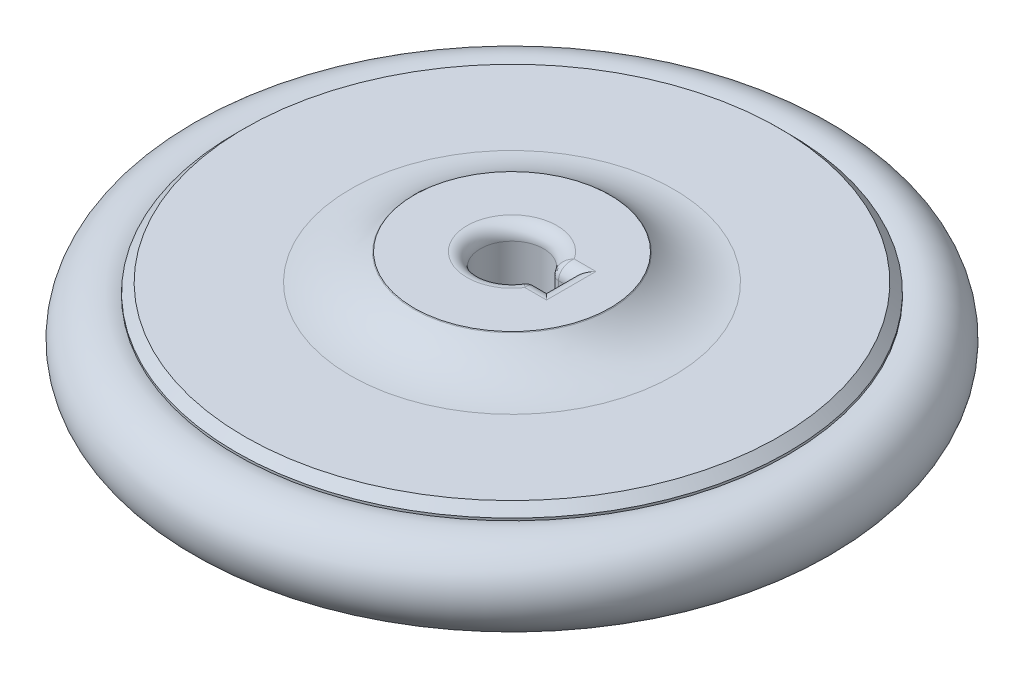
SolidWorks part; units mm, degrees
ref_plane "Спереди" through (0, 0, 0) normal (0, 0, 1) x (1, 0, 0)
ref_plane "Сверху" through (0, 0, 0) normal (0, 1, 0) x (1, 0, 0)
ref_plane "Справа" through (0, 0, 0) normal (1, 0, 0) x (0, 0, -1)
sketch "Эскиз1" plane through (0, 0, 0) normal (0, 1, 0) x (1, 0, 0)
  circle A0 centre (0, 0) radius 62
  dimension "D1" = 124
extrude "Бобышка-Вытянуть1" add sketch "Эскиз1" along normal blind 22
sketch "Эскиз3" plane through (0, 0, 0) normal (0, 0, 1) x (1, 0, 0)
  line L0 (0, 0) -> (0, 22) construction
  line L1 (62, 22) -> (-62, 22) construction
  line L2 (0, 22) -> (0, 11) construction
  line L3 (0, 11) -> (-84.2443, 11) construction
  line L9 (-56, -6.4426) -> (-56, 31.0537) construction
  circle A2 centre (-65, 11) radius 9
  dimension "D1" = 56
  dimension "D2" = 18
revolve "Вырез-Повернуть2" cut sketch "Эскиз3" angle 360 about L0
chamfer "Фаска3" distance 2 angle 45 1 edges at (0, 0, 62)
chamfer "Фаска2" distance 2 angle 45 1 edges at (0, 22, 62)
sketch "Эскиз4" plane through (0, 22, 0) normal (0, 1, 0) x (1, 0, 0)
  circle A0 centre (0, 0) radius 18
  dimension "D1" = 36
extrude "Бобышка-Вытянуть2" add sketch "Эскиз4" along normal blind 6
chamfer "Фаска4" distance 10 angle 45 1 edges at (0, 22, 18)
fillet "Скругление1" radius 20 1 edges at (0, 22, 28)
sketch "Эскиз5" plane through (0, 28, 0) normal (0, 1, 0) x (1, 0, 0)
  circle A0 centre (0, 0) radius 7.1
  dimension "D1" = 14.2
extrude "Вырез-Вытянуть1" cut sketch "Эскиз5" against normal blind 24
sketch "Эскиз6" plane through (0, 0, 0) normal (0, -1, 0) x (1, 0, 0)
  circle A0 centre (0, 0) radius 2.3
  dimension "D1" = 4.6
extrude "Вырез-Вытянуть2" cut sketch "Эскиз6" against normal through all
chamfer "Фаска8" distance 2 angle 45 1 edges at (0, 0, -2.3)
sketch "Эскиз7" plane through (0, 28, 0) normal (0, 1, 0) x (1, 0, 0)
  line L0 (0, 30.9089) -> (0, 0) construction
  line L1 (0, 0) -> (66.8313, 0) construction
  line L2 (10.3, 2.55) -> (10.3, -2.55)
  line L3 (10.3, 2.55) -> (0, 2.55)
  line L4 (0, 2.55) -> (0, -2.55)
  line L5 (10.3, -2.55) -> (0, -2.55)
  point P10 (0, 0)
  point P11 (10.3, 0)
  dimension "D1" = 10.3
  dimension "D2" = 5.1
extrude "Вырез-Вытянуть3" cut sketch "Эскиз7" against normal up to surface (24 mm away) up to face at (0, 4, 2.3)
fillet "Скругление2" radius 2 2 edges at (6.6263, 16, 2.55) (6.6263, 16, -2.55)
fillet "Скругление3" radius 3 6 edges at (9.0904, 28, -2.55) (6.8808, 28, -2.8179) (9.0904, 28, 2.55) (6.8808, 28, 2.8179) (10.3, 28, 0) (-7.1, 28, 0)
sketch "Эскиз8" plane through (0, 28, 0) normal (0, 1, 0) x (1, 0, 0)
  circle A0 centre (0, 0) radius 18.7332
extrude "Вырез-Вытянуть-Тонкостенный1" [suppressed] cut sketch "Эскиз8" against normal blind 50 thin thin type one direction wall 50
chamfer "Фаска9" [suppressed] distance 1 angle 45
sketch "Эскиз9" plane through (0, 0, 0) normal (0, 0, 1) x (1, 0, 0)
  line L0 (0, -4.5016) -> (0, 44.7819) construction
  circle A1 centre (-65, 11) radius 9
  arc A2 (-62, 2.5147) -> (-62, 19.4853) centre (-65, 11) ccw construction
revolve "ШИНА" add sketch "Эскиз9" angle 360 about L0
